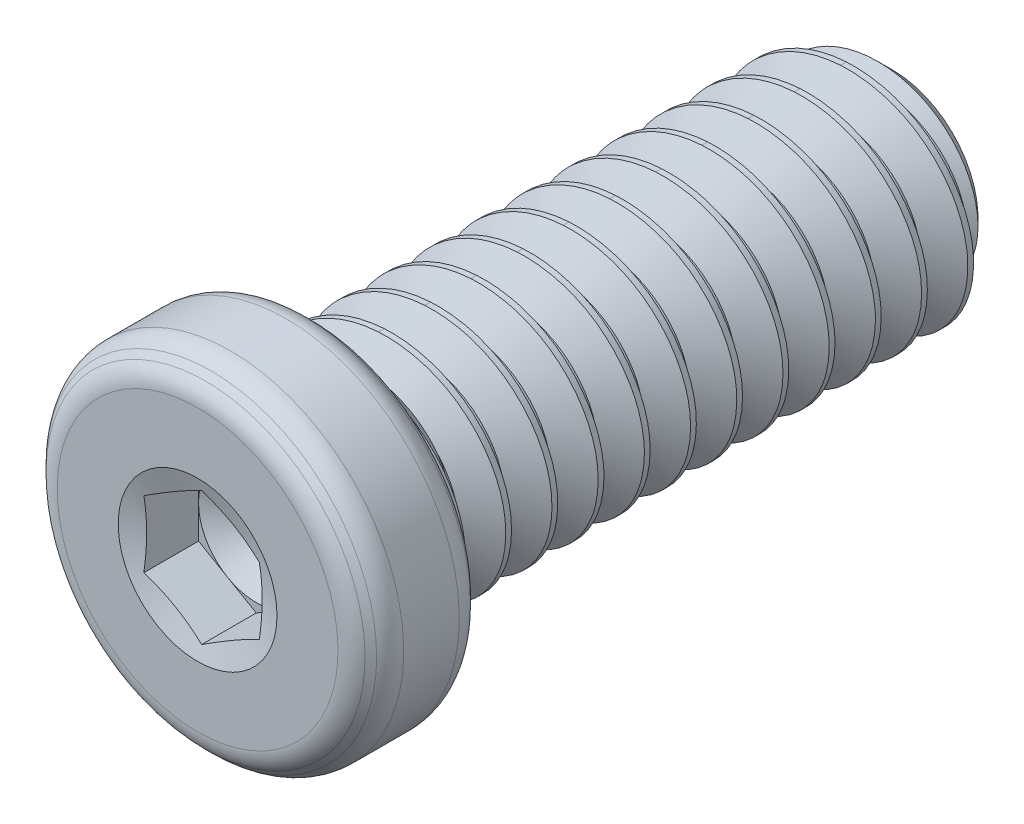
SolidWorks part; units mm, degrees
ref_plane "Front Plane" through (0, 0, 0) normal (0, 0, 1) x (1, 0, 0)
ref_plane "Top Plane" through (0, 0, 0) normal (0, 1, 0) x (1, 0, 0)
ref_plane "Right Plane" through (0, 0, 0) normal (1, 0, 0) x (0, 0, -1)
sketch "Sketch1" plane through (0, 0, 0) normal (1, 0, 0) x (0, 0, -1)
  line L0 (-9.5504, 0) -> (9.5504, 0) construction
  line L1 (-9.5504, 0) -> (-9.5504, 4.7625)
  line L2 (-9.5504, 4.7625) -> (-6.3246, 4.7625)
  line L3 (-6.3246, 4.7625) -> (-6.3246, 3.175)
  line L4 (-6.3246, 3.175) -> (8.7255, 3.175)
  line L5 (9.471, 3.3125) -> (10.106, 2.2126) construction
  line L6 (10.106, 2.2126) -> (10.741, 3.3125) construction
  line L7 (10.741, 3.3125) -> (9.471, 3.3125) construction
  line L8 (8.7255, 3.175) -> (9.5504, 2.3501)
  line L9 (9.5504, 2.3501) -> (9.5504, 0)
  line L10 (9.5504, 3.175) -> (10.6617, 3.175) construction
  line L11 (10.106, 3.3125) -> (10.106, 3.175) construction
  line L12 (10.106, 3.175) -> (10.106, 2.3501) construction
  line L13 (10.106, 2.3501) -> (10.106, 2.2126) construction
  line L14 (10.0267, 2.3501) -> (10.1854, 2.3501)
  line L15 (9.5107, 3.2437) -> (10.7013, 3.2437)
  line L16 (10.1854, 2.3501) -> (10.7013, 3.2437)
  line L17 (10.0267, 2.3501) -> (9.5107, 3.2437)
  line L18 (-9.5504, 1.5875) -> (-7.9375, 1.5875)
  line L19 (-7.9375, 1.5875) -> (-7.9375, 0)
  line L20 (5.1054, 3.175) -> (5.1054, -3.175) construction
  point P20 (10.106, 3.2437)
  point P22 (5.1054, -3.175)
  point P28 (5.1054, 0)
  point P29 (8.7255, -3.175)
  point P30 (-7.1311, 4.7625)
  dimension "Head Diameter" = 9.525
  dimension "Length" = 15.875
  dimension "Head Height" = 3.2258
  dimension "Screw Size Decimal Equivalent" = 6.35
  dimension "D1" = 45
  dimension "Thread Pitch" = 1.27
  dimension "D3" = 0.1588
  dimension "Drive Size" = 3.175
  dimension "D4" = 4.445
  dimension "D5" = 1.6129
  dimension "D2" = 2.4193
sketch "Sketch3" plane through (0, 0, 0) normal (1, 0, 0) x (0, 0, -1)
  line L0 (-9.5504, 3.859) -> (-9.5504, 1.5875)
  line L1 (-9.5504, 1.5875) -> (-7.9375, 1.5875)
  line L2 (-7.9375, 1.5875) -> (-7.9375, 0)
  line L3 (-7.9375, 0) -> (9.5504, 0)
  line L4 (9.5504, 0) -> (9.5504, 2.3501)
  line L5 (9.5504, 2.3501) -> (8.7255, 3.175)
  line L6 (8.7255, 3.175) -> (-6.3246, 3.175)
  line L7 (-6.3246, 3.175) -> (-6.3246, 4.122)
  line L8 (-7.1192, 4.7625) -> (-8.6469, 4.7625)
  line L9 (-9.3324, 4.3851) -> (-9.173, 4.5445)
  line L10 (-6.593, 4.5445) -> (-6.4336, 4.3851)
  line L11 (-9.5504, 4.7625) -> (-6.3246, 4.7625) construction
  arc A0 (-9.173, 4.5445) -> (-8.6469, 4.7625) centre (-8.6469, 4.0184) cw
  arc A1 (-9.3324, 4.3851) -> (-9.5504, 3.859) centre (-8.8063, 3.859) ccw
  arc A2 (-6.4336, 4.3851) -> (-6.3246, 4.122) centre (-6.6967, 4.122) cw
  arc A3 (-6.593, 4.5445) -> (-7.1192, 4.7625) centre (-7.1192, 4.0184) ccw
  point P25 (-9.5504, 4.1672)
  dimension "D1" = 45
  dimension "D3" = 0.7441
  dimension "D2" = 0.5953
revolve "Revolve1" add sketch "Sketch3" angle 360 about L0
sketch "Sketch4" plane through (0, 0, 9.5504) normal (0, 0, 1) x (1, 0, 0)
  line L1 (0, 1.8331) -> (-1.5875, 0.9165)
  line L2 (-1.5875, 0.9165) -> (-1.5875, -0.9165)
  line L3 (-1.5875, -0.9165) -> (0, -1.8331)
  line L4 (0, -1.8331) -> (1.5875, -0.9165)
  line L5 (1.5875, -0.9165) -> (1.5875, 0.9165)
  line L6 (1.5875, 0.9165) -> (0, 1.8331)
  circle A0 centre (0, 0) radius 1.5875 construction
extrude "Cut-Extrude1" cut sketch "Sketch4" against normal up to vertex (1.6129 mm away) up to point (0, 1.5875, 7.9375)
sketch "Sketch5" plane through (0, 0, 9.5504) normal (0, 0, 1) x (1, 0, 0)
  circle A0 centre (0, 0) radius 2.1828
  circle A1 centre (0, 0) radius 4.7625 construction
  dimension "D1" = 4.3656
extrude "Cut-Extrude2" cut sketch "Sketch5" against normal up to next (1.6129 mm away) draft 72.5
sketch "Sketch10" plane through (0, 0, 7.9375) normal (0, 0, 1) x (1, 0, 0)
  line L0 (1.5875, 0.9165) -> (1.5875, -0.9165) construction
  circle A0 centre (0, 0) radius 1.5875
extrude "Cut-Extrude3" cut sketch "Sketch10" against normal through all draft 60
split "Split1" bodies to split 112 resulting bodies 107 108 split by face at (0, -4.122, 6.3246)
sketch "Sketch6" plane through (0, 0, -9.5504) normal (0, 0, -1) x (-1, 0, 0)
  circle A0 centre (0, 0) radius 3.175 construction
  circle A1 centre (0, 0) radius 3.175
curve "Helix/Spiral1" pitch 1.27 height 16.51 radius 3.175 centre (0, 0, -9.5504) axis (0, 0, 1) start towards (0, 1, 0)
sketch "Sketch7" plane through (0, 0, 0) normal (1, 0, 0) x (0, 0, -1)
  line L0 (10.0267, 2.3501) -> (10.1854, 2.3501) construction
  line L1 (10.0267, 2.3501) -> (9.5107, 3.2437) construction
  line L2 (9.5107, 3.2437) -> (10.7013, 3.2437) construction
  line L3 (10.1854, 2.3501) -> (10.7013, 3.2437) construction
  line L4 (10.0267, 2.3501) -> (10.1854, 2.3501)
  line L5 (10.0267, 2.3501) -> (9.5107, 3.2437)
  line L6 (9.5107, 3.2437) -> (10.7013, 3.2437)
  line L7 (10.1854, 2.3501) -> (10.7013, 3.2437)
sweep "Cut-Sweep1" cut profiles "Sketch7" path "Helix/Spiral1" align with end faces yes
sketch "Sketch11" plane through (0, 0, 0) normal (1, 0, 0) x (0, 0, -1)
  line L0 (-6.3246, 3.4925) -> (-6.0071, 3.175)
  line L1 (-6.3246, 4.7625) -> (-6.3246, 3.175) construction
  line L2 (-6.3246, 3.175) -> (8.7255, 3.175) construction
  line L3 (-6.0071, 3.175) -> (-5.6896, 3.175)
  line L4 (-5.6896, 3.175) -> (-2.5146, 0)
  line L5 (-9.5504, 0) -> (9.5504, 0) construction
  line L6 (-2.5146, 0) -> (-6.3246, 0)
  line L7 (-6.3246, 0) -> (-6.3246, 3.4925) construction
  line L8 (-6.3246, 3.4925) -> (-7.021, 3.4925)
  line L9 (-7.021, 3.4925) -> (-7.021, 0)
  line L10 (-7.021, 0) -> (-6.3246, 0)
  dimension "D1" = 45
  dimension "D2" = 0.3175
  dimension "D3" = 45
  dimension "D4" = 0.635
revolve "Revolve2" add sketch "Sketch11" angle 360 about L6
equation "\"D3@Sketch1\" = \"Thread Pitch@Sketch1\" / 8"
equation "\"D4@Sketch1\" = \"Thread Pitch@Sketch1\" * 3.5"
equation "\"D3@Helix/Spiral1\"=\"Length@Sketch1\" +( \"Thread Pitch@Sketch1\"*0.5)"
equation "\"D4@Helix/Spiral1\" = \"Thread Pitch@Sketch1\""
equation "\"D5@Sketch1\"=\"Head Height@Sketch1\"*0.5"
equation "\"D2@Sketch3\"=\"Head Diameter@Sketch1\"*0.0625"
equation "\"D2@Sketch11\"=\"Thread Pitch@Sketch1\" / 4"
equation "\"D3@Sketch3\"=\"D2@Sketch3\"*1.25"
equation "\"D2@Sketch1\"=\"Head Height@Sketch1\"*0.75"
equation "\"D4@Sketch11\"=\"Thread Pitch@Sketch1\"*0.5"
equation "\"D4@Sketch3\"=\"D3@Sketch3\"*0.5"
equation "\"D1@Sketch5\"=\"Drive Size@Sketch1\"*1.375"
